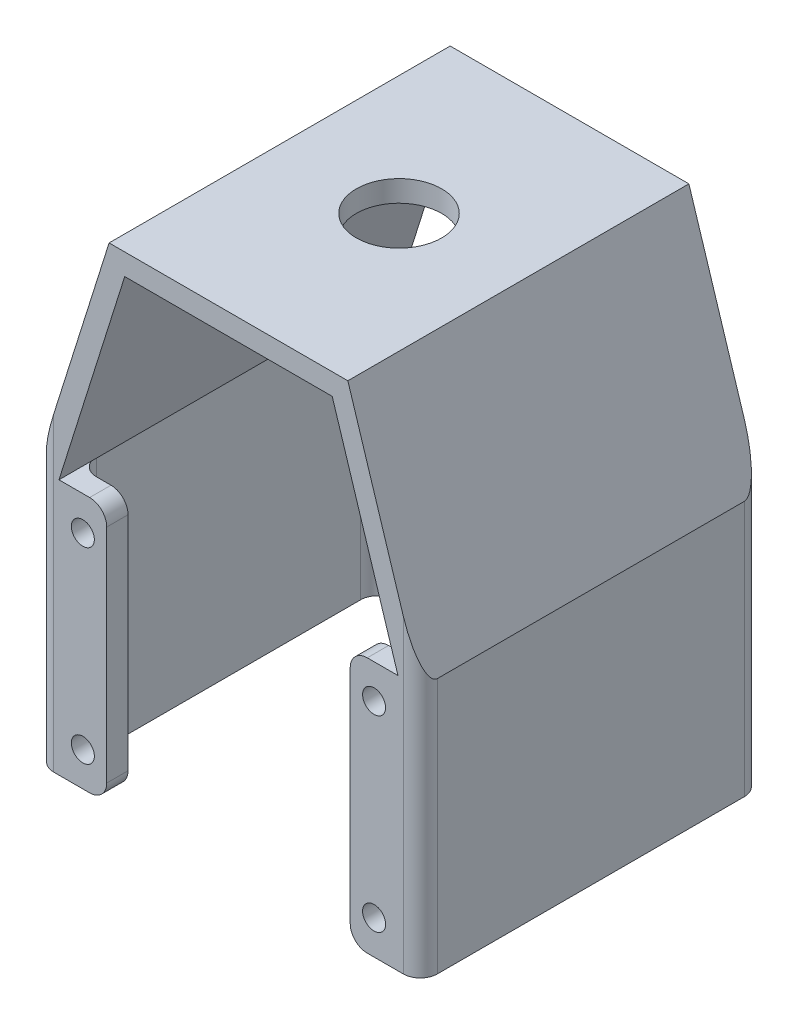
SolidWorks part; units mm, degrees
ref_plane "Plano frontal" through (0, 0, 0) normal (0, 0, 1) x (1, 0, 0)
ref_plane "Plano superior" through (0, 0, 0) normal (0, 1, 0) x (1, 0, 0)
ref_plane "Plano direito" through (0, 0, 0) normal (1, 0, 0) x (0, 0, -1)
sketch "Esboço1" plane through (0, 0, 0) normal (0, 0, 1) x (1, 0, 0)
  line L1 (-22.5, 28.5) -> (22.5, 28.5)
  line L2 (-22.5, 28.5) -> (-22.5, -28.5)
  line L3 (-22.5, -28.5) -> (22.5, -28.5)
  line L4 (22.5, 28.5) -> (22.5, -28.5)
  line L5 (-22.5, 28.5) -> (22.5, -28.5) construction
  line L6 (-22.5, -28.5) -> (22.5, 28.5) construction
  point P0 (0, 0)
  dimension "D1" = 45
  dimension "D2" = 57
extrude "Ressalto-extrusão1" add sketch "Esboço1" along normal blind 40
sketch "Esboço2" plane through (0, 28.5, 0) normal (0, 1, 0) x (1, 0, 0)
  circle A0 centre (0, -20) radius 14
sketch "Esboço3" plane through (0, 0, 0) normal (0, 0, -1) x (-1, 0, 0)
  line L0 (-22.5, 1.5) -> (-22.5, 28.5)
  line L1 (-22.5, -28.5) -> (-22.5, 28.5) construction
  line L2 (-22.5, 1.5) -> (-14, 28.5)
  line L3 (14, 28.5) -> (-14, 28.5) construction
  line L4 (-22.5, 28.5) -> (22.5, 28.5) construction
  line L5 (-22.5, 28.5) -> (-14, 28.5)
  line L6 (22.5, 28.5) -> (22.5, -28.5) construction
  line L7 (22.5, 1.5) -> (14, 28.5)
  line L8 (22.5, 1.5) -> (22.5, 28.5)
  line L9 (22.5, 28.5) -> (14, 28.5)
  dimension "D1" = 28.3064
  dimension "D2" = 28.3064
  dimension "D3" = 27
  dimension "D4" = 27
extrude "Corte-extrusão1" cut sketch "Esboço3" against normal through all
sketch "Esboço4" plane through (0, -28.5, 0) normal (0, -1, 0) x (1, 0, 0)
  line L9 (-20, 37.5) -> (-20, 2.5)
  line L12 (20, 37.5) -> (20, 2.5)
  line L16 (20, 2.5) -> (11, 2.5)
  line L17 (20, 37.5) -> (11, 37.5)
  line L18 (-20, 2.5) -> (-11, 2.5)
  line L19 (-20, 37.5) -> (-11, 37.5)
  line L20 (11, 2.5) -> (11, 0)
  line L21 (-22.5, 0) -> (22.5, 0) construction
  line L22 (11, 0) -> (-11, 0)
  line L23 (-11, 0) -> (-11, 2.5)
  line L24 (11, 37.5) -> (11, 40)
  line L25 (-22.5, 40) -> (22.5, 40) construction
  line L26 (11, 40) -> (-11, 40)
  line L27 (-11, 40) -> (-11, 37.5)
sketch "Esboço5" plane through (0, 0, 0) normal (0, 0, -1) x (-1, 0, 0)
  line L3 (-19.879, 1.5) -> (-12.1661, 26)
  line L4 (-12.1661, 26) -> (12.1661, 26)
  line L5 (12.1661, 26) -> (19.879, 1.5)
  line L6 (-19.879, 1.5) -> (19.879, 1.5)
extrude "Corte-extrusão3" cut sketch "Esboço5" against normal through all
extrude "Corte-extrusão5" cut sketch "Esboço4" against normal blind 30
sketch "Esboço7" plane through (0, 0, 0) normal (0, 0, -1) x (-1, 0, 0)
  line L0 (-11, 1.5) -> (-11, -28.5) construction
  line L1 (-19.879, 1.5) -> (-11, 1.5) construction
  line L2 (-11, -28.5) -> (-22.5, -28.5) construction
  line L3 (11, 1.5) -> (11, -28.5) construction
  line L5 (11, 1.5) -> (19.879, 1.5) construction
  line L6 (22.5, -28.5) -> (11, -28.5) construction
  line L9 (-11, 1.5) -> (-11, -28.5)
  line L11 (-16.2436, -13.4484) -> (-12.8748, -13.4484)
  line L15 (14.279, 1.5) -> (14.279, -28.5)
  line L16 (-14.279, 1.5) -> (-14.279, -28.5)
  line L17 (-14.279, -28.5) -> (-11, -28.5)
  line L18 (-14.279, 1.5) -> (-11, 1.5)
  line L19 (14.279, -28.5) -> (11, -28.5)
  line L20 (11, -28.5) -> (11, 1.5)
  line L21 (11, 1.5) -> (14.279, 1.5)
  circle A0 centre (-15.8, -2.5) radius 1.35
  circle A1 centre (-15.8, -24.5) radius 1.35
  circle A2 centre (15.8, -2.5) radius 1.35
  circle A3 centre (15.8, -24.5) radius 1.35
  dimension "D1" = 2.7
  dimension "D2" = 2.7
  dimension "D3" = 4.8
  dimension "D4" = 4
  dimension "D5" = 4.8
  dimension "D6" = 4
  dimension "D7" = 4.8
  dimension "D8" = 2.7
  dimension "D9" = 4
  dimension "D10" = 4.8
  dimension "D11" = 2.7
  dimension "D12" = 4
sketch "Esboço8" plane through (0, 28.5, 0) normal (0, 1, 0) x (1, 0, 0)
  circle A0 centre (0, -20) radius 5
  dimension "D1" = 10
extrude "Corte-extrusão7" cut sketch "Esboço8" against normal through all
fillet "Filete1" radius 2 8 edges at (11, -28.5, 38.75) (-11, -28.5, 38.75) (-11, -28.5, 1.25) (11, -28.5, 1.25) (-11, 1.5, 1.25) (-11, 1.5, 38.75) (11, 1.5, 38.75) (11, 1.5, 1.25)
fillet "Filete2" radius 2 8 edges at (22.5, -13.5, 0) (22.5, -13.5, 40) (-22.5, -13.5, 40) (-22.5, -13.5, 0) (-20, -13.5, 2.5) (20, -13.5, 2.5) (-20, -13.5, 37.5) (20, -13.5, 37.5)
extrude "Corte-extrusão8" cut sketch "Esboço7" against normal through all
sketch "Esboço9" plane through (0, 0, 0) normal (0, 0, -1) x (-1, 0, 0)
  line L0 (-14.279, 1.5) -> (-14.279, -28.5) construction
  line L1 (-14.279, -28.5) -> (-20.5, -28.5) construction
  line L3 (0, 28.5) -> (0, -30.4556)
  line L4 (14, 28.5) -> (-14, 28.5) construction
  circle A0 centre (-17.079, -2.5) radius 1.35
  circle A1 centre (-17.079, -24.5) radius 1.35
  circle A2 centre (17.079, -24.5) radius 1.35
  circle A3 centre (17.079, -2.5) radius 1.35
  dimension "D1" = 2.7
  dimension "D2" = 2.7
  dimension "D3" = 22
  dimension "D4" = 2.8
  dimension "D5" = 2.8
  dimension "D6" = 4
extrude "Corte-extrusão9" cut sketch "Esboço9" against normal through all contours A1 | A0 | A3 | A2
fillet "Filete3" radius 2 8 edges at (-14.279, -28.5, 1.25) (-14.279, -28.5, 38.75) (14.279, -28.5, 1.25) (14.279, -28.5, 38.75) (-14.279, 1.5, 1.25) (-14.279, 1.5, 38.75) (14.279, 1.5, 38.75) (14.279, 1.5, 1.25)
